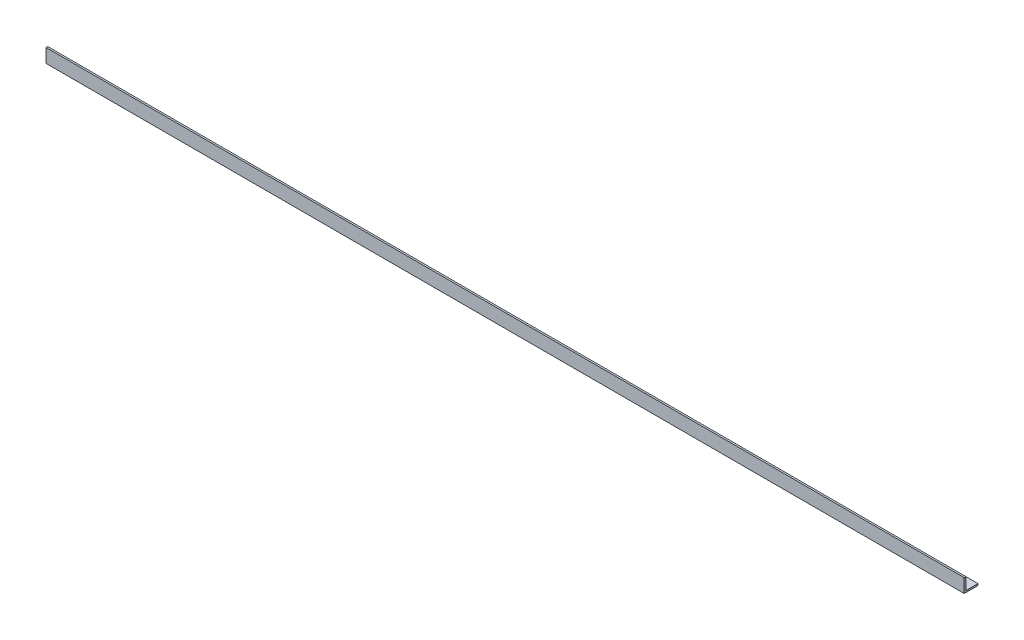
SolidWorks part; units mm, degrees
ref_plane "Спереди" through (0, 0, 0) normal (0, 0, 1) x (1, 0, 0)
ref_plane "Сверху" through (0, 0, 0) normal (0, 1, 0) x (1, 0, 0)
ref_plane "Справа" through (0, 0, 0) normal (1, 0, 0) x (0, 0, -1)
sketch "Эскиз1" plane through (0, 0, 0) normal (1, 0, 0) x (0, 0, -1)
  line L0 (0, 40) -> (0, 0)
  line L1 (0, 0) -> (40, 0)
extrude "Вытянуть-Тонкостенный1" add sketch "Эскиз1" along normal blind 2665 thin thin type one direction reverse wall 5
